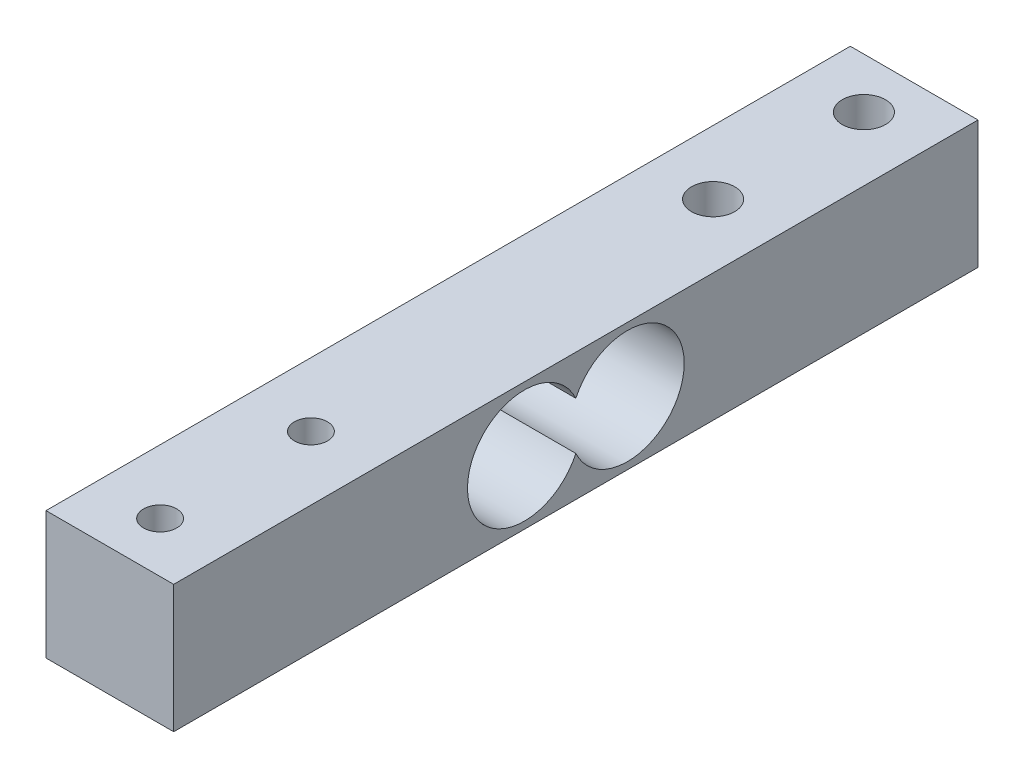
SolidWorks part; units mm, degrees
ref_plane "Front Plane" through (0, 0, 0) normal (0, 0, 1) x (1, 0, 0)
ref_plane "Top Plane" through (0, 0, 0) normal (0, 1, 0) x (1, 0, 0)
ref_plane "Right Plane" through (0, 0, 0) normal (1, 0, 0) x (0, 0, -1)
sketch "Sketch1" plane through (0, 0, 0) normal (0, 0, 1) x (1, 0, 0)
  line L1 (-6.35, -6.35) -> (6.35, -6.35)
  line L2 (-6.35, -6.35) -> (-6.35, 6.35)
  line L3 (-6.35, 6.35) -> (6.35, 6.35)
  line L4 (6.35, -6.35) -> (6.35, 6.35)
  point P8 (0, -6.35)
  point P9 (-6.35, 0)
  dimension "D1" = 12.7
  dimension "D2" = 12.7
extrude "Boss-Extrude1" add sketch "Sketch1" along normal mid plane 80
sketch "Sketch2" plane through (6.35, 0, 0) normal (1, 0, 0) x (0, 0, -1)
  line L0 (-40, -6.35) -> (-40, 6.35) construction
  line L1 (-5.1266, 0) -> (5.1266, 0) construction
  line L2 (-40, -6.35) -> (40, -6.35) construction
  arc A0 (0, 2.375) -> (0, -2.375) centre (-5.1266, 0) ccw
  arc A1 (0, -2.375) -> (0, 2.375) centre (5.1266, 0) ccw
  point P7 (-40, 0)
  point P9 (0, -6.35)
  point P10 (0, 0)
  dimension "D1" = 11.3
  dimension "D2" = 4.75
extrude "Cut-Extrude1" cut sketch "Sketch2" against normal through all
sketch "Sketch3" plane through (0, 6.35, 0) normal (0, 1, 0) x (1, 0, 0)
  line L0 (-6.35, 40) -> (6.35, 40) construction
  circle A0 centre (0, 35) radius 2.15
  circle A1 centre (0, 20) radius 2.15
  dimension "D3" = 4.3
  dimension "D2" = 5
  dimension "D1" = 15
extrude "Cut-Extrude2" cut sketch "Sketch3" against normal through all
sketch "Sketch4" plane through (0, 6.35, 0) normal (0, 1, 0) x (1, 0, 0)
  line L0 (6.35, -40) -> (-6.35, -40) construction
  circle A0 centre (0, -35) radius 1.65
  circle A1 centre (0, -20) radius 1.65
  point P8 (0, -40)
  dimension "D3" = 3.3
  dimension "D1" = 5
  dimension "D2" = 15
extrude "Cut-Extrude3" cut sketch "Sketch4" against normal through all
sketch "Sketch8" plane through (0, -6.35, 0) normal (0, -1, 0) x (1, 0, 0)
  line L0 (-6.35, -15) -> (6.35, -15)
  line L1 (-6.35, 40) -> (-6.35, -40) construction
  line L2 (6.35, 40) -> (6.35, -40) construction
  line L4 (-6.35, 15) -> (6.35, 15)
  line L5 (-6.35, 40) -> (6.35, 40) construction
  line L6 (-6.35, -40) -> (6.35, -40) construction
  dimension "D1" = 25
  dimension "D2" = 25
split line "Split Line4"
sketch "Sketch9" plane through (0, 0, 0) normal (0, 1, 0) x (1, 0, 0)
  line L0 (-6.35, -27.5) -> (6.35, -27.5) construction
  line L1 (-6.35, -40) -> (-6.35, 40) construction
  line L2 (6.35, -40) -> (6.35, 40) construction
  line L3 (6.35, -40) -> (-6.35, -40) construction
  dimension "D1" = 12.5
ref_axis "Axis1" through (-6.35, 0, 27.5) along (1, 0, 0)
ref_axis "Axis2" through (0, 0, -4) along (0, 0, 1)
sketch "Sketch10" plane through (0, 0, 0) normal (0, 1, 0) x (1, 0, 0)
  line L0 (0, 35) -> (0, 20) construction
  line L1 (0, 27.5) -> (-6.35, 27.5) construction
  line L2 (-6.35, -40) -> (-6.35, 40) construction
  point P4 (0, 27.5)
ref_axis "Axis3" through (0, 0, -27.5) along (-1, 0, 0)
